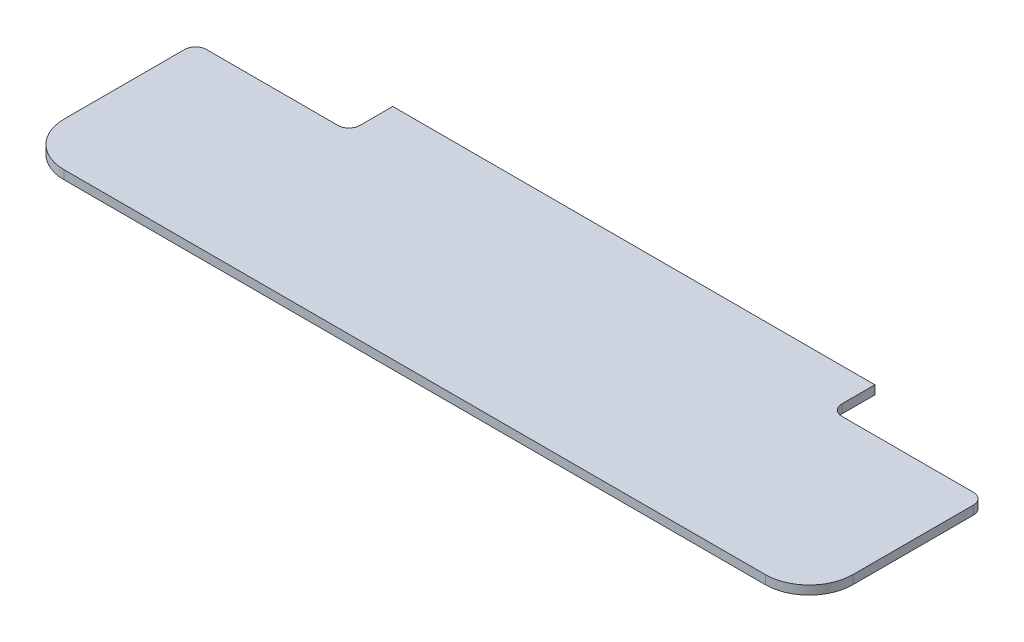
SolidWorks part; units mm, degrees
ref_plane "前视基准面" through (0, 0, 0) normal (0, 0, 1) x (1, 0, 0)
ref_plane "上视基准面" through (0, 0, 0) normal (0, 1, 0) x (1, 0, 0)
ref_plane "右视基准面" through (0, 0, 0) normal (1, 0, 0) x (0, 0, -1)
other "Configuration Table"
sketch "草图1" plane through (0, 0, 0) normal (0, 1, 0) x (1, 0, 0)
  line L1 (-180, -50) -> (180, -50)
  line L2 (-180, -50) -> (-180, 50)
  line L3 (-180, 50) -> (180, 50)
  line L4 (180, -50) -> (180, 50)
  line L5 (-180, -50) -> (180, 50) construction
  line L6 (-180, 50) -> (180, -50) construction
  point P0 (0, 0)
  dimension "D1" = 360
  dimension "D2" = 100
extrude "凸台-拉伸1" add sketch "草图1" along normal blind 4
fillet "圆角3" radius 20 2 edges at (-180, 2, 50) (180, 2, 50)
sketch "草图4" plane through (0, 4, 0) normal (0, 1, 0) x (1, 0, 0)
  line L0 (0, 0) -> (0, 50) construction
  line L1 (-180, 50) -> (-110, 50)
  line L2 (-180, 50) -> (-180, 30)
  line L3 (-180, 30) -> (-110, 30)
  line L4 (-110, 50) -> (-110, 30)
  line L5 (180, 50) -> (-180, 50) construction
  line L6 (180, 30) -> (110, 30)
  line L7 (110, 50) -> (110, 30)
  line L8 (180, 50) -> (110, 50)
  line L9 (180, 50) -> (180, 30)
  dimension "D1" = 70
  dimension "D2" = 20
extrude "切除-拉伸2" cut sketch "草图4" against normal blind 6
fillet "圆角5" radius 5 4 edges at (180, 2, -30) (110, 2, -30) (-110, 2, -30) (-180, 2, -30)
